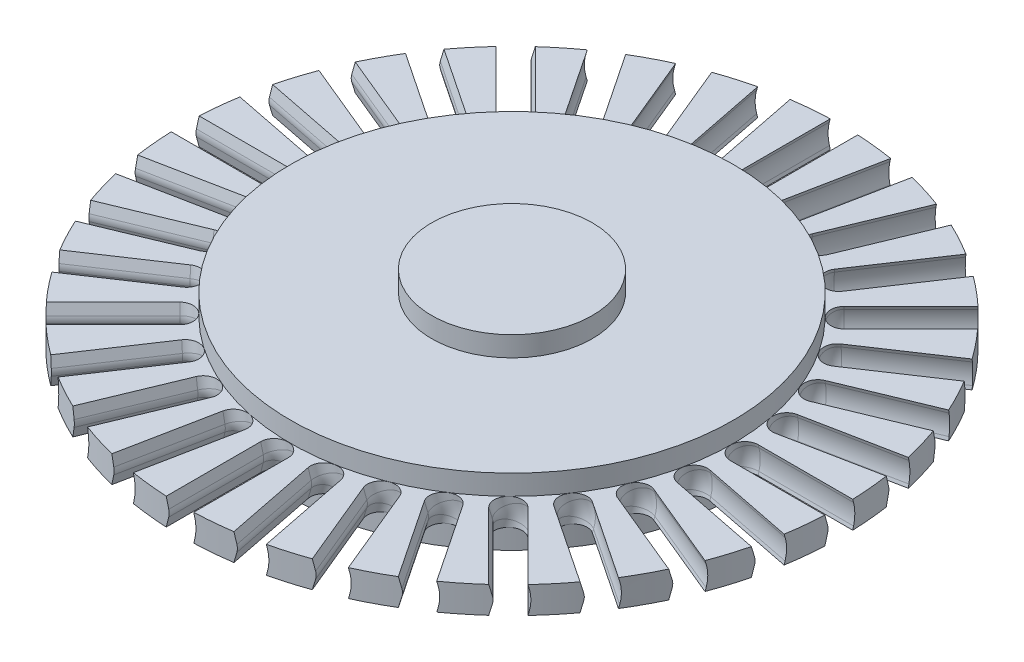
SolidWorks part; units mm, degrees
material "AISI 316 Annealed Stainless Steel Bar (SS)"
ref_plane "Front Plane" through (0, 0, 0) normal (0, 0, 1) x (1, 0, 0)
ref_plane "Top Plane" through (0, 0, 0) normal (0, 1, 0) x (1, 0, 0)
ref_plane "Right Plane" through (0, 0, 0) normal (1, 0, 0) x (0, 0, -1)
ref_axis "Axis1" through (0, 13.97, 0) along (0, -1, 0)
sketch "Sketch4" plane through (0, 0, 0) normal (0, 0, 1) x (1, 0, 0)
  line L1 (78.1558, -3.175) -> (78.1558, 3.175)
  line L2 (78.1558, 3.175) -> (52.5018, 3.175)
  line L4 (0, -12.7) -> (0, 12.7)
  line L6 (0, 0) -> (0, 12.7) construction
  line L9 (52.5018, -3.175) -> (78.1558, -3.175)
  line L12 (19.05, -12.7) -> (19.05, 12.7)
  line L16 (52.5018, 3.175) -> (52.5018, -3.175)
  line L18 (19.05, -12.7) -> (0, -12.7)
  line L20 (0, 12.7) -> (19.05, 12.7)
  line L22 (0, 0) -> (78.1558, 0) construction
  line L23 (19.05, 7.9375) -> (52.5018, 7.9375)
  line L24 (52.5018, 7.9375) -> (52.5018, 3.175)
  line L25 (19.05, -7.9375) -> (52.5018, -7.9375)
  line L26 (52.5018, -7.9375) -> (52.5018, -3.175)
  point P6 (0, 0)
  point P11 (78.1558, 0)
  dimension "D1" = 156.3116
  dimension "D3" = 6.35
  dimension "D4" = 105.0036
  dimension "D8" = 38.1
  dimension "D5" = 25.4
  dimension "D6" = 15.875
revolve "Disc" add sketch "Sketch4" angle 360 about L6
ref_plane "Plane1" through (78.1558, 0, 0) normal (1, 0, 0) x (0, 0, -1)
sketch "Endmill" plane through (0, 0, 0) normal (0, 1, 0) x (1, 0, 0)
  line L0 (103.3018, 3.175) -> (55.6768, 3.175)
  line L1 (55.6768, -3.175) -> (103.3018, -3.175)
  line L2 (103.3018, -3.175) -> (103.3018, 3.175)
  line L3 (0, 0) -> (52.5018, 0) construction
  arc A0 (55.6768, 3.175) -> (55.6768, -3.175) centre (55.6768, 0) ccw
  dimension "D1" = 6.35
  dimension "D2" = 52.5018
  dimension "D3" = 50.8
sketch "Sketch9" plane through (78.1558, 0, 0) normal (1, 0, 0) x (0, 0, -1)
  line L0 (-3.1169, 12.7) -> (-0.2078, 1.6114)
  line L1 (-0.2078, -1.6114) -> (-3.1169, -12.7)
  line L2 (0, 12.7) -> (0, -12.7) construction
  arc A0 (-0.2078, 1.6114) -> (-0.2078, -1.6114) centre (-6.35, 0) cw
  point P4 (0, 0)
  point P10 (0, 0)
  dimension "D2" = 6.35
  dimension "D1" = 14.7
  dimension "D3" = 25.4
sweep "Blade Cutout" cut profiles "Endmill" path "Sketch9"
pattern_circular "Blades" count 32 over 360 about axis through (0, 13.97, 0) along (0, -1, 0) of "Blade Cutout"
sketch "Sketch7" plane through (0, 0, 0) normal (0, 1, 0) x (1, 0, 0)
  line L0 (38.1, 0) -> (63.5, 0) construction
  line L1 (38.1, 3.175) -> (63.5, 3.175)
  line L2 (38.1, -3.175) -> (63.5, -3.175)
  arc A0 (38.1, 3.175) -> (38.1, -3.175) centre (38.1, 0) ccw
  arc A1 (63.5, -3.175) -> (63.5, 3.175) centre (63.5, 0) ccw
  point P3 (50.8, 0)
  dimension "D1" = 3.175
  dimension "D2" = 63.5
  dimension "D3" = 25.4
extrude "Mass Cutout" [suppressed] cut sketch "Sketch7" against normal through all both and the other way through all
pattern_circular "Cutouts" [suppressed] count 16 over 360 about axis through (0, 13.97, 0) along (0, -1, 0) of bodies 117
equation "\"D1@Sketch4\"=2*\"rotor tip@[TP] [Turb] Turbine.Assembly\""
equation "\"D4@Sketch4\"=2*\"rotor base@[TP] [Turb] Turbine.Assembly\""
equation "\"D2@Endmill\"=\"rotor base@[TP] [Turb] Turbine.Assembly\""
equation "\"D1@Endmill\"=\"blade gap@[TP] [Turb] Turbine.Assembly\""
equation "\"D1@Sketch9\"=\"blade angle@[TP] [Turb] Turbine.Assembly\""
equation "\"D2@Sketch9\"=\"blade gap@[TP] [Turb] Turbine.Assembly\""
